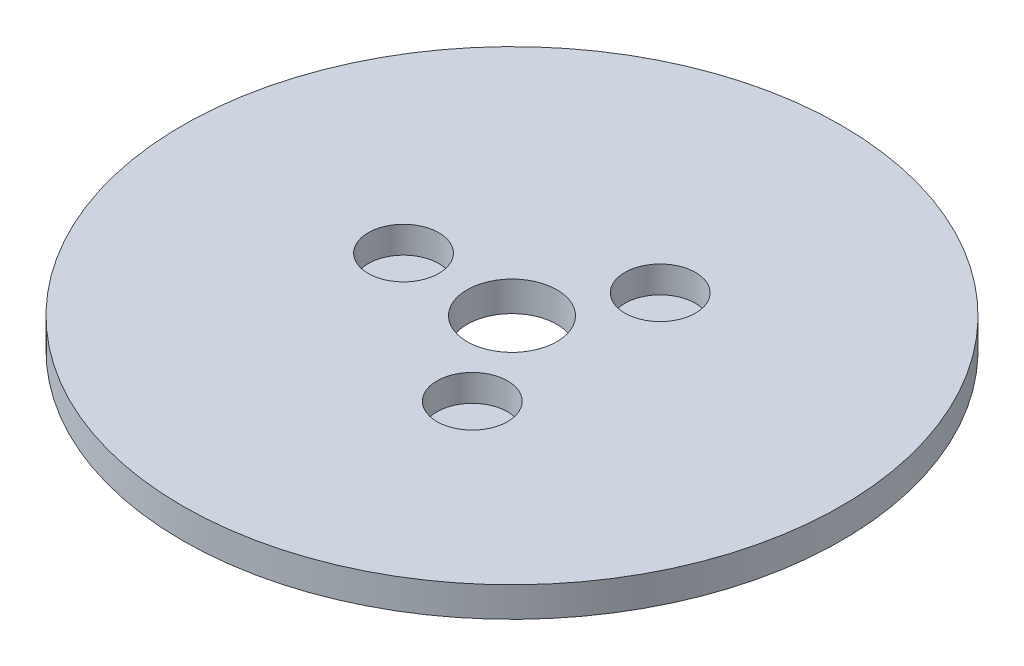
SolidWorks part; units mm, degrees
ref_plane "Front Plane" through (0, 0, 0) normal (0, 0, 1) x (1, 0, 0)
ref_plane "Top Plane" through (0, 0, 0) normal (0, 1, 0) x (1, 0, 0)
ref_plane "Right Plane" through (0, 0, 0) normal (1, 0, 0) x (0, 0, -1)
sketch "Sketch1" plane through (0, 0, 0) normal (0, 1, 0) x (1, 0, 0)
  circle A0 centre (0, 0) radius 55
  dimension "FLANGE_OD" = 110
extrude "Boss-Extrude1" add sketch "Sketch1" along normal blind 5
sketch "Sketch2" plane through (0, 0, 0) normal (0, 1, 0) x (1, 0, 0)
  circle A0 centre (0, 0) radius 7.5
  dimension "BORE_D" = 15
extrude "Cut-Extrude1" cut sketch "Sketch2" along normal through all
sketch "Sketch3" plane through (0, 5, 0) normal (0, 1, 0) x (1, 0, 0)
  circle A0 centre (0, 0) radius 18.1037 construction
  circle A1 centre (-18.1037, 0) radius 5.8939
  dimension "BOLT_D" = 11.7877
  dimension "BOLT_PCD" = 36.2073
extrude "Cut-Extrude2" cut sketch "Sketch3" against normal blind 4.4656
pattern_circular "CirPattern1" count 3 over 360 about axis through (0, 0, 0) along (0, 1, 0) of "Cut-Extrude2"
